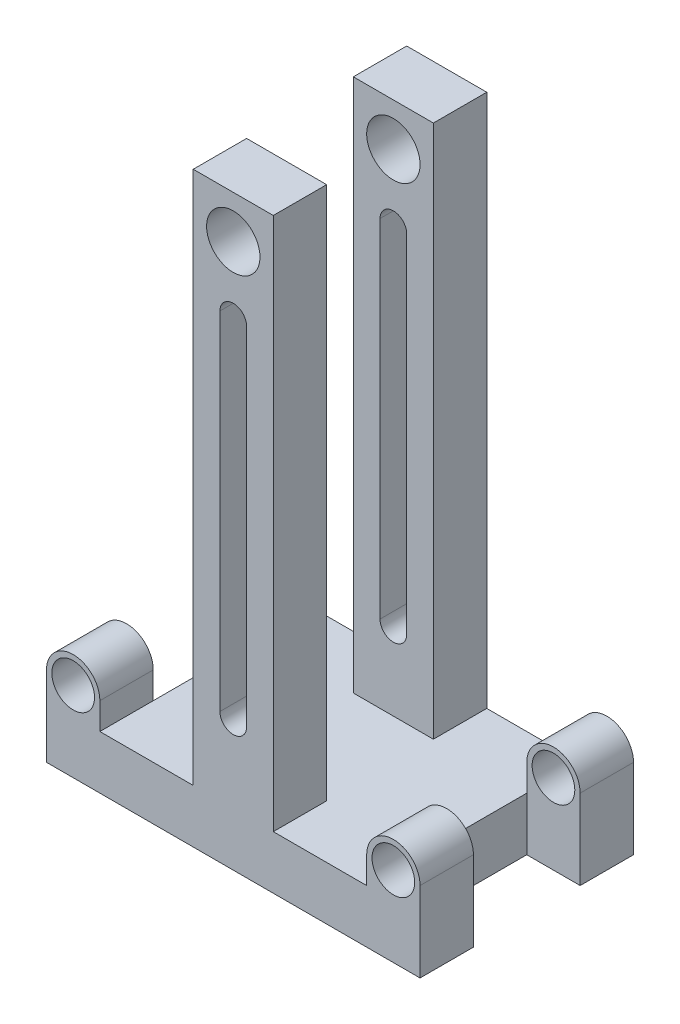
SolidWorks part; units mm, degrees
ref_plane "Front Plane" through (0, 0, 0) normal (0, 0, 1) x (1, 0, 0)
ref_plane "Top Plane" through (0, 0, 0) normal (0, 1, 0) x (1, 0, 0)
ref_plane "Right Plane" through (0, 0, 0) normal (1, 0, 0) x (0, 0, -1)
sketch "Sketch1" plane through (0, 0, 0) normal (0, 0, 1) x (1, 0, 0)
  line L1 (88.9, -12.7) -> (-88.9, -12.7)
  line L2 (88.9, -12.7) -> (88.9, 12.7)
  line L3 (88.9, 12.7) -> (-88.9, 12.7)
  line L4 (-88.9, -12.7) -> (-88.9, 12.7)
  line L5 (88.9, -12.7) -> (-88.9, 12.7) construction
  line L6 (88.9, 12.7) -> (-88.9, -12.7) construction
  line L7 (-19.05, 12.7) -> (19.05, 12.7)
  line L8 (-19.05, 12.7) -> (-19.05, 266.7)
  line L9 (-19.05, 266.7) -> (19.05, 266.7)
  line L10 (19.05, 12.7) -> (19.05, 266.7)
  line L11 (-6.35, 49.53) -> (6.35, 49.53)
  line L12 (-6.35, 49.53) -> (-6.35, 214.63)
  line L13 (-6.35, 214.63) -> (6.35, 214.63)
  line L14 (6.35, 49.53) -> (6.35, 214.63)
  line L15 (-6.35, 49.53) -> (6.35, 214.63) construction
  line L16 (-6.35, 214.63) -> (6.35, 49.53) construction
  circle A0 centre (0, 246.38) radius 12.7
  arc A1 (6.35, 214.63) -> (-6.35, 214.63) centre (0, 214.63) ccw
  arc A2 (6.35, 49.53) -> (-6.35, 49.53) centre (0, 49.53) cw
  point P0 (0, 0)
  point P10 (0, 266.7)
  point P13 (0, 132.08)
  dimension "D5" = 20.32
  dimension "D6" = 25.4
  dimension "D7" = 12.7
  dimension "D1" = 177.8
  dimension "D2" = 25.4
  dimension "D3" = 254
  dimension "D4" = 38.1
  dimension "D8" = 165.1
  dimension "D9" = 114.3
extrude "Boss-Extrude1" add sketch "Sketch1" along normal blind 25.4 contours L3 L10 L9 L8 A0 | L4 L1 L2 L3 region at (0, 0, 0) region at (0, 15.2684, 0)
extrude "Boss-Extrude2" add sketch "Sketch1<4>" along normal blind 101.6 contours L4 L1 L2 L3 region at (0, 0, 0)
sketch "Sketch1<4>" plane through (0, 0, 0) normal (0, 0, 1) x (1, 0, 0) same geometry as "Sketch1"
extrude "Boss-Extrude3" add sketch "Sketch1<5>" against normal blind 25.4 from surface contours L3 L10 L9 L8 A0 region at (0, 15.2684, 0) starting at face at (0, 0, 101.6)
sketch "Sketch1<5>" plane through (0, 0, 0) normal (0, 0, 1) x (1, 0, 0) same geometry as "Sketch1"
sketch "Sketch2" plane through (0, 0, 101.6) normal (0, 0, 1) x (1, 0, 0)
  line L0 (-19.05, 12.7) -> (-88.9, 12.7) construction
  line L1 (-88.9, -12.7) -> (-88.9, 12.7) construction
  line L2 (-88.9, 25.4) -> (-88.9, 12.7)
  line L3 (-88.9, 12.7) -> (-63.5, 12.7)
  line L4 (-63.5, 12.7) -> (-63.5, 25.4)
  circle A0 centre (-76.2, 25.4) radius 12.7
  circle A1 centre (-76.2, 25.4) radius 10.16
  line M10 (-19.05, 12.7) -> (-88.9, 12.7)
  dimension "D1" = 25.4
  dimension "D2" = 2.54
extrude "Boss-Extrude4" add sketch "Sketch2" against normal through all contours A0 A1 | A0 L2 L3 | A0 L4 M10 region at (-86.0632, 15.5368, 101.6) region at (-76.2, 37.7408, 101.6) region at (-66.3368, 15.5368, 101.6)
sketch "Sketch3" plane through (0, 12.7, 0) normal (0, 1, 0) x (1, 0, 0)
  line L0 (-63.5, 0) -> (-63.5, -101.6) construction
  line L1 (-88.9, -25.4) -> (-63.5, -25.4)
  line L2 (-88.9, -25.4) -> (-88.9, -76.2)
  line L3 (-88.9, -76.2) -> (-63.5, -76.2)
  line L4 (-63.5, -25.4) -> (-63.5, -76.2)
  line L5 (-88.9, -25.4) -> (-63.5, -76.2) construction
  line L6 (-88.9, -76.2) -> (-63.5, -25.4) construction
  line L7 (-19.05, -25.4) -> (19.05, -25.4) construction
  line L8 (-19.05, -76.2) -> (19.05, -76.2) construction
  line L9 (-88.9, 0) -> (-88.9, -101.6) construction
  point P0 (-76.2, -50.8)
extrude "Cut-Extrude1" cut sketch "Sketch3" against normal through all both and the other way through all
mirror "Mirror1" about plane through (0, 0, 0) normal (1, 0, 0) of "Cut-Extrude1", "Boss-Extrude4"
equation "\"l\"=5"
